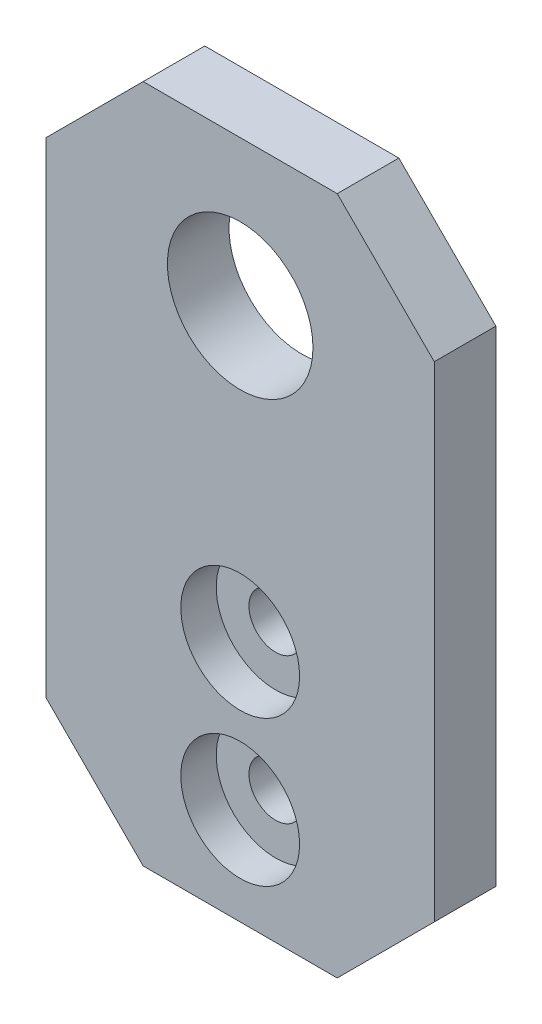
SolidWorks part; units mm, degrees
material "6061 Alloy"
ref_plane "Front Plane" through (0, 0, 0) normal (0, 0, 1) x (1, 0, 0)
ref_plane "Top Plane" through (0, 0, 0) normal (0, 1, 0) x (1, 0, 0)
ref_plane "Right Plane" through (0, 0, 0) normal (1, 0, 0) x (0, 0, -1)
sketch "Sketch1" plane through (0, 0, 0) normal (0, 0, 1) x (1, 0, 0)
  line L0 (0, 35) -> (0, -35) construction
  line L1 (-20, -35) -> (20, -35)
  line L2 (-20, -35) -> (-20, 35)
  line L3 (-20, 35) -> (20, 35)
  line L4 (20, -35) -> (20, 35)
  line L5 (-20, -35) -> (20, 35) construction
  line L6 (-20, 35) -> (20, -35) construction
  circle A0 centre (0, 20) radius 7.5
  circle A1 centre (0, -10) radius 2.5 construction
  circle A2 centre (0, -25) radius 2.5 construction
  point P4 (0, 0)
  dimension "D3" = 15
  dimension "D4" = 5
  dimension "D5" = 5
  dimension "D1" = 40
  dimension "D2" = 70
  dimension "D6" = 10
  dimension "D7" = 15
  dimension "D8" = 55
extrude "Boss-Extrude1" add sketch "Sketch1" along normal blind 6.35
hole_wizard "CBORE for M5 Hex Head Cap Screw1" positions "Sketch4" profile "Sketch5" counterbore size "M5" standard "ANSI Metric" end condition through all
sketch "Sketch4" plane through (0, 0, 6.35) normal (0, 0, 1) x (1, 0, 0)
  point P0 (0, -10)
  point P3 (0, -25)
sketch "Sketch5" plane through (0, -10, 6.35) normal (1, 0, 0) x (0, -1, 0)
  line L0 (0, 0) -> (0, 6.35)
  line L1 (0, 6.35) -> (2.75, 6.35)
  line L3 (2.75, 6.35) -> (2.75, 3.65)
  line L4 (2.75, 3.65) -> (6.12, 3.65)
  line L5 (6.12, 3.65) -> (6.12, 0)
  line L7 (6.12, 0) -> (0, 0)
  line L11 (0, -6.35) -> (0, 107.95) construction
  dimension "Thru Hole Dia." = 5.5
  dimension "Thru Hole Depth" = 6.35
  dimension "C'Bore Dia." = 12.24
  dimension "C'Bore Depth" = 3.65
chamfer "Chamfer1" distance 10 angle 45 4 edges at (20, -35, 3.175) (-20, -35, 3.175) (20, 35, 3.175) (-20, 35, 3.175)
